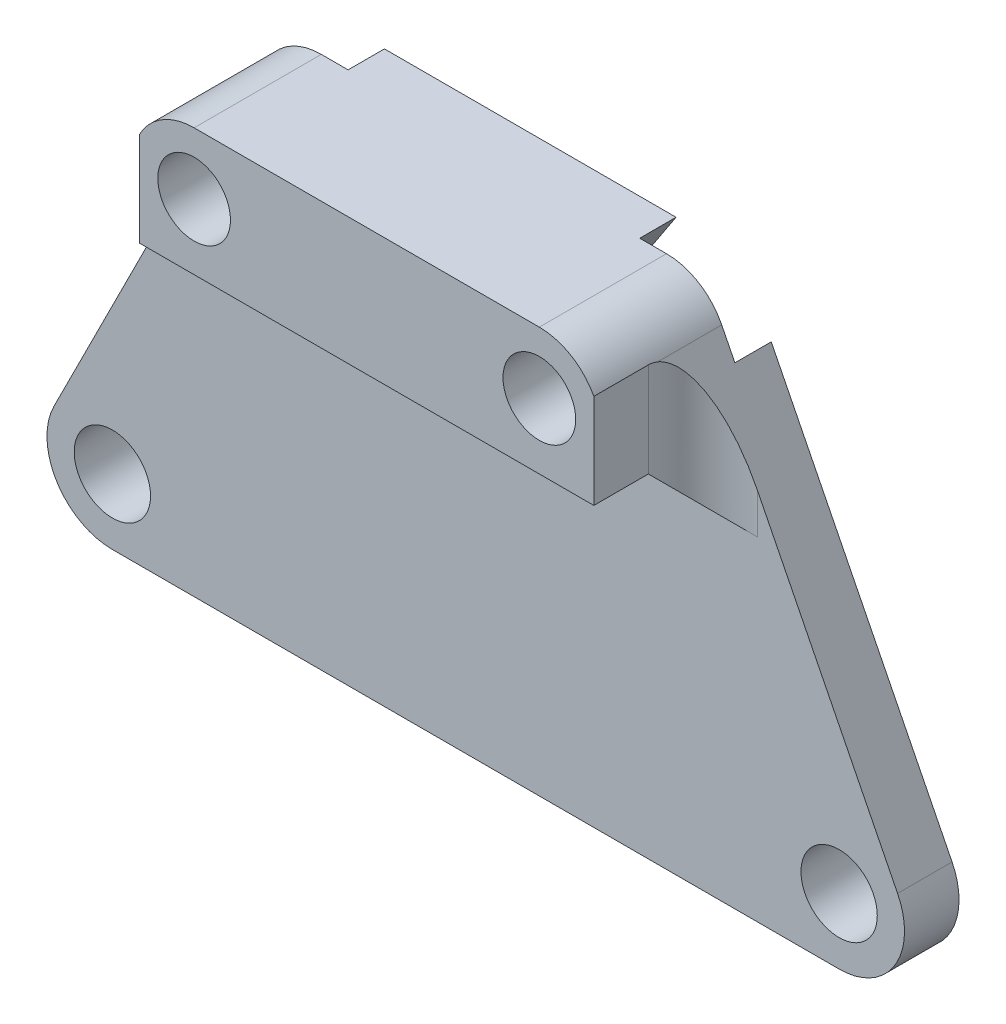
SolidWorks part; units mm, degrees
ref_plane "Front Plane" through (0, 0, 0) normal (0, 0, 1) x (1, 0, 0)
ref_plane "Top Plane" through (0, 0, 0) normal (0, 1, 0) x (1, 0, 0)
ref_plane "Right Plane" through (0, 0, 0) normal (1, 0, 0) x (0, 0, -1)
sketch "Sketch1" plane through (0, 0, 0) normal (0, 0, 1) x (1, 0, 0)
  line L0 (27, 29.0964) -> (0, 29.0964) construction
  line L1 (54, 36.0964) -> (0, 36.0964)
  line L2 (54, 36.0964) -> (54, 0)
  line L3 (54, 0) -> (0, 0)
  line L4 (0, 36.0964) -> (0, 0)
  line L5 (27, 11.1418) -> (27, 47.9509) construction
  line L8 (30, 162.0964) -> (30, -184.4036) construction
  line L11 (54, 19.0964) -> (54, 10.0964) construction
  circle A0 centre (36.5, 32.6964) radius 2
  circle A1 centre (17.5, 32.6964) radius 2
  circle A2 centre (47, 11.3464) radius 2.1
  circle A3 centre (7, 11.3464) radius 2.1
  dimension "D3" = 4
  dimension "D4" = 4
  dimension "D8" = 4.2
  dimension "D9" = 4.2
  dimension "D1" = 19
  dimension "D2" = 3.4
  dimension "D5" = 7
  dimension "D6" = 3
  dimension "D7" = 9.5
extrude "Boss-Extrude1" add sketch "Sketch1" along normal blind 3
sketch "Sketch2" plane through (0, 0, 3) normal (0, 0, 1) x (1, 0, 0)
  line L0 (39.5, 36.0964) -> (14.5, 36.0964)
  line L1 (39.5, 36.0964) -> (39.5, 29.0964)
  line L2 (39.5, 29.0964) -> (14.5, 29.0964)
  line L3 (14.5, 36.0964) -> (14.5, 29.0964)
  line L4 (27, 57.3453) -> (27, -24.4522) construction
  line L5 (54, 36.0964) -> (0, 36.0964) construction
  circle A0 centre (36.5, 32.6964) radius 2 construction
  circle A1 centre (17.5, 32.6964) radius 2 construction
  circle A2 centre (17.5, 32.6964) radius 2
  circle A3 centre (36.5, 32.6964) radius 2
  point P6 (-14.7981, 51.5696)
  dimension "D1" = 7
  dimension "D2" = 25
  dimension "D3" = 12.5
  dimension "D4" = 9.5
extrude "Boss-Extrude2" add sketch "Sketch2" along normal blind 6
chamfer "Chamfer1" distance 3 angle 45 1 edges at (27, 29.0964, 3)
sketch "Sketch3" plane through (0, 0, 3) normal (0, 0, 1) x (1, 0, 0)
  line L0 (47, 7.7464) -> (7, 7.7464)
  line L2 (3.783, 12.9622) -> (14.4617, 34.2224)
  line L6 (36.5, 36.0964) -> (17.5, 36.0964)
  line L7 (39.5383, 34.2224) -> (50.217, 12.9622)
  arc A0 (47, 7.7464) -> (50.217, 12.9622) centre (47, 11.3464) ccw
  circle A1 centre (47, 11.3464) radius 2.1 construction
  arc A2 (3.783, 12.9622) -> (7, 7.7464) centre (7, 11.3464) ccw
  circle A3 centre (7, 11.3464) radius 2.1 construction
  arc A4 (39.5383, 34.2224) -> (36.5, 36.0964) centre (36.5, 32.6964) ccw
  arc A5 (17.5, 36.0964) -> (14.4617, 34.2224) centre (17.5, 32.6964) ccw
  point P10 (20.3252, 34.588)
  point P20 (33.4454, 34.2224)
  point P24 (16.0295, 36.0964)
  dimension "D1" = 1.5
  dimension "D2" = 1.5
  dimension "D3" = 6.8
  dimension "D4" = 6.8
extrude "Cut-Extrude1" cut sketch "Sketch3" against normal up to next (3 mm away) and the other way up to next (6 mm away) flip side to cut
fillet "Fillet2" radius 3 2 edges at (14.5, 30.1964, 3) (39.5, 30.1964, 3)
sketch "Sketch4" plane through (0, 0, 0) normal (0, 0, -1) x (-1, 0, 0)
  line L0 (-36.5, 36.0964) -> (-17.5, 36.0964) construction
  line L1 (-38.1067, 29.4976) -> (-34.5332, 29.7056)
  line L2 (-34.5332, 29.7056) -> (-32.9265, 32.9043)
  line L3 (-32.9265, 32.9043) -> (-34.8933, 35.8951)
  line L6 (-40.0735, 32.4884) -> (-38.1067, 29.4976)
  line L15 (-40.0735, 32.4884) -> (-40.9583, 33.8338)
  line L16 (-34.8933, 35.8951) -> (-35.7781, 37.2404)
  line L17 (-40.9583, 33.8338) -> (-35.7781, 37.2404)
  line L18 (-27, 1.2901) -> (-27, 41.6446) construction
  line L19 (-38.4668, 35.6871) -> (-39.2702, 34.0878) [skipped]
  line L20 (-34.8933, 35.8951) -> (-36.6801, 35.7911) [skipped]
  line L21 (-13.0417, 33.8338) -> (-18.2219, 37.2404)
  line L22 (-19.1067, 35.8951) -> (-18.2219, 37.2404)
  line L23 (-13.9265, 32.4884) -> (-13.0417, 33.8338)
  line L24 (-13.9265, 32.4884) -> (-15.8933, 29.4976)
  line L25 (-21.0735, 32.9043) -> (-19.1067, 35.8951)
  line L26 (-19.4668, 29.7056) -> (-21.0735, 32.9043)
  line L27 (-15.8933, 29.4976) -> (-19.4668, 29.7056)
  arc A0 (-39.0901, 30.993) -> (-33.9099, 34.3997) centre (-36.5, 32.6964) ccw construction
  arc A1 (-14.9099, 30.993) -> (-20.0901, 34.3997) centre (-17.5, 32.6964) cw construction
  arc A2 (-36.5, 36.0964) -> (-39.5383, 34.2224) centre (-36.5, 32.6964) ccw construction
  dimension "D1" = 6.2
  dimension "D3" = 56.67
  dimension "D4" = 9.5
extrude "Cut-Extrude2" cut sketch "Sketch4" against normal blind 2
